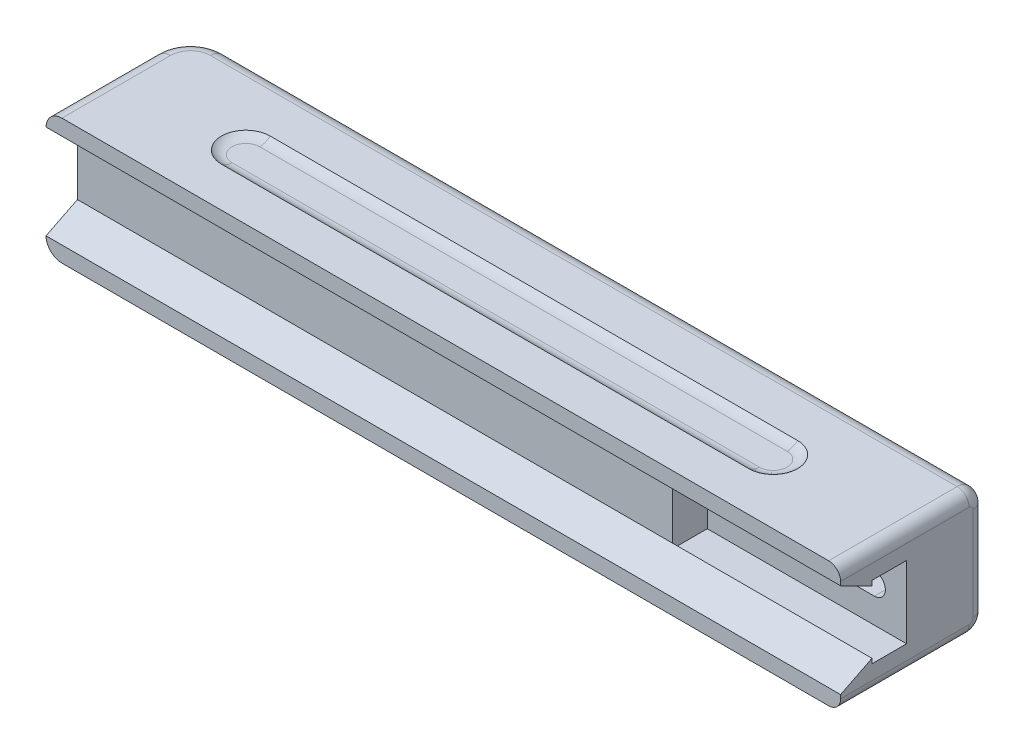
SolidWorks part; units mm, degrees
ref_plane "Front Plane" through (0, 0, 0) normal (0, 0, 1) x (1, 0, 0)
ref_plane "Top Plane" through (0, 0, 0) normal (0, 1, 0) x (1, 0, 0)
ref_plane "Right Plane" through (0, 0, 0) normal (1, 0, 0) x (0, 0, -1)
sketch "Sketch1" plane through (0, 0, 0) normal (0, 0, 1) x (1, 0, 0)
  line L0 (0, 0) -> (256.8448, 0)
  line L1 (256.8448, 0) -> (256.8448, 39.9974)
  line L2 (256.8448, 39.9974) -> (0, 39.9974)
  line L3 (0, 39.9974) -> (0, 0)
  dimension "D1" = 256.8448
  dimension "D2" = 39.9974
extrude "Boss-Extrude1" add sketch "Sketch1" along normal blind 45.9994
sketch "Sketch2" plane through (256.8448, 0, 0) normal (1, 0, 0) x (0, 0, -1)
  line L0 (-35.9994, 10) -> (-45.9994, 4.9987)
  line L1 (-45.9994, 0) -> (0, 0) construction
  line L2 (-45.9994, 0) -> (-45.9994, 39.9974) construction
  line L3 (-45.9994, 4.9987) -> (-45.9994, 34.9987)
  line L4 (-35.9994, 10) -> (-35.9994, 29.9999)
  line L5 (-35.9994, 29.9999) -> (-45.9994, 34.9987)
  dimension "D1" = 10
  dimension "D2" = 10
  dimension "D3" = 5.0013
  dimension "D4" = 20
  dimension "D5" = 29.9999
extrude "Cut-Extrude1" cut sketch "Sketch2" against normal through all
sketch "Sketch3" plane through (256.8448, 0, 0) normal (1, 0, 0) x (0, 0, -1)
  line L0 (-45.9994, 0) -> (0, 0) construction
  line L1 (-35.9994, 8.4938) -> (-24.9809, 8.4938)
  line L2 (-24.9809, 8.4938) -> (-24.9809, 31.4935)
  line L3 (-24.9809, 31.4935) -> (-35.9994, 31.4935)
  line L4 (-35.9994, 31.4935) -> (-35.9994, 8.4938)
  dimension "D1" = 8.4938
  dimension "D2" = 11.0185
  dimension "D3" = 22.9997
extrude "Cut-Extrude2" cut sketch "Sketch3" against normal blind 67.2744
sketch "Sketch4" plane through (0, 0, 24.9809) normal (0, 0, 1) x (1, 0, 0)
  line L0 (189.5704, 31.4935) -> (256.8448, 31.4935) construction
  line L1 (189.5704, 8.4938) -> (189.5704, 31.4935) construction
  circle A0 centre (198.7728, 19.9936) radius 3.4963
  dimension "D2" = 6.9926
  dimension "D1" = 11.4998
  dimension "D3" = 9.2024
extrude "Cut-Extrude3" cut sketch "Sketch4" against normal through all
sketch "Sketch5" plane through (0, 0, 24.9809) normal (0, 0, 1) x (1, 0, 0)
  line L0 (189.5704, 31.4935) -> (256.8448, 31.4935) construction
  line L1 (189.5704, 8.4938) -> (189.5704, 31.4935) construction
  line L2 (242.7783, 23.4861) -> (225.7857, 23.4861)
  line L4 (225.7857, 16.5011) -> (242.7783, 16.5011)
  arc A0 (225.7857, 23.4861) -> (225.7857, 16.5011) centre (225.7857, 19.9936) ccw
  arc A1 (242.7783, 16.5011) -> (242.7783, 23.4861) centre (242.7783, 19.9936) ccw
  dimension "D3" = 6.985
  dimension "D4" = 6.985
  dimension "D1" = 11.4998
  dimension "D2" = 11.4998
  dimension "D5" = 16.9926
  dimension "D6" = 36.2153
extrude "Cut-Extrude4" cut sketch "Sketch5" against normal through all
sketch "Sketch6" plane through (256.8448, 0, 0) normal (1, 0, 0) x (0, 0, -1)
  line L0 (0, 39.9974) -> (-45.9994, 39.9974)
  line L1 (-45.9994, 39.9974) -> (-45.9994, 0)
  line L2 (-45.9994, 0) -> (0, 0)
  line L3 (0, 0) -> (0, 39.9974)
extrude "Cut-Extrude5" cut sketch "Sketch6" against normal blind 3.81
fillet "Fillet1" radius 3.81 3 edges at (253.0348, 0, 22.9997) (253.0348, 39.9974, 22.9997) (253.0348, 19.9987, 0)
fillet "Fillet2" radius 11.43 1 edges at (0, 19.9987, 0)
fillet "Fillet3" radius 5.08 8 edges at (251.9189, 38.8815, 1.1159) (251.9189, 1.1159, 1.1159) (0, 0, 28.7147) (3.3478, 0, 3.3478) (0, 39.9974, 28.7147) (3.3478, 39.9974, 3.3478) (130.3274, 0, 0) (130.3274, 39.9974, 0)
sketch "Sketch7" plane through (0, 39.9974, 0) normal (0, 1, 0) x (1, 0, 0)
  line L0 (211.1248, -33.2994) -> (43.18, -33.2994)
  line L1 (249.2248, -45.9994) -> (5.08, -45.9994) construction
  line L2 (43.18, -17.78) -> (211.1248, -17.78)
  line L3 (249.2248, -5.08) -> (11.43, -5.08) construction
  line L4 (249.2248, -45.9994) -> (249.2248, -5.08) construction
  line L5 (5.08, -11.43) -> (5.08, -45.9994) construction
  arc A5 (211.1248, -33.2994) -> (211.1248, -17.78) centre (211.1248, -25.5397) ccw
  arc A6 (43.18, -17.78) -> (43.18, -33.2994) centre (43.18, -25.5397) ccw
  dimension "D1" = 12.7
  dimension "D2" = 12.7
  dimension "D3" = 38.1
  dimension "D4" = 38.1
  dimension "D5" = 38.1
  dimension "D6" = 38.1
extrude "Cut-Extrude6" cut sketch "Sketch7" against normal blind 1.27
fillet "Fillet4" radius 5.08 4 edges at (127.1524, 38.7274, 33.2994) (35.4203, 38.7274, 25.5397) (127.1524, 38.7274, 17.78) (218.8845, 38.7274, 25.5397)
sketch "Sketch8" plane through (0, 0, 0) normal (0, -1, 0) x (1, 0, 0)
  line L0 (43.18, 33.2994) -> (211.1248, 33.2994)
  line L1 (249.2248, 5.08) -> (249.2248, 45.9994) construction
  line L2 (211.1248, 17.78) -> (43.18, 17.78)
  line L3 (5.08, 45.9994) -> (5.08, 11.43) construction
  line L4 (5.08, 45.9994) -> (249.2248, 45.9994) construction
  line L5 (11.43, 5.08) -> (249.2248, 5.08) construction
  arc A0 (211.1248, 17.78) -> (211.1248, 33.2994) centre (211.1248, 25.5397) ccw
  arc A1 (43.18, 33.2994) -> (43.18, 17.78) centre (43.18, 25.5397) ccw
  dimension "D1" = 38.1
  dimension "D2" = 38.1
  dimension "D3" = 38.1
  dimension "D4" = 38.1
  dimension "D5" = 12.7
  dimension "D6" = 12.7
extrude "Cut-Extrude7" cut sketch "Sketch8" against normal blind 1.27
fillet "Fillet5" radius 5.08 4 edges at (127.1524, 1.27, 33.2994) (218.8845, 1.27, 25.5397) (127.1524, 1.27, 17.78) (35.4203, 1.27, 25.5397)
